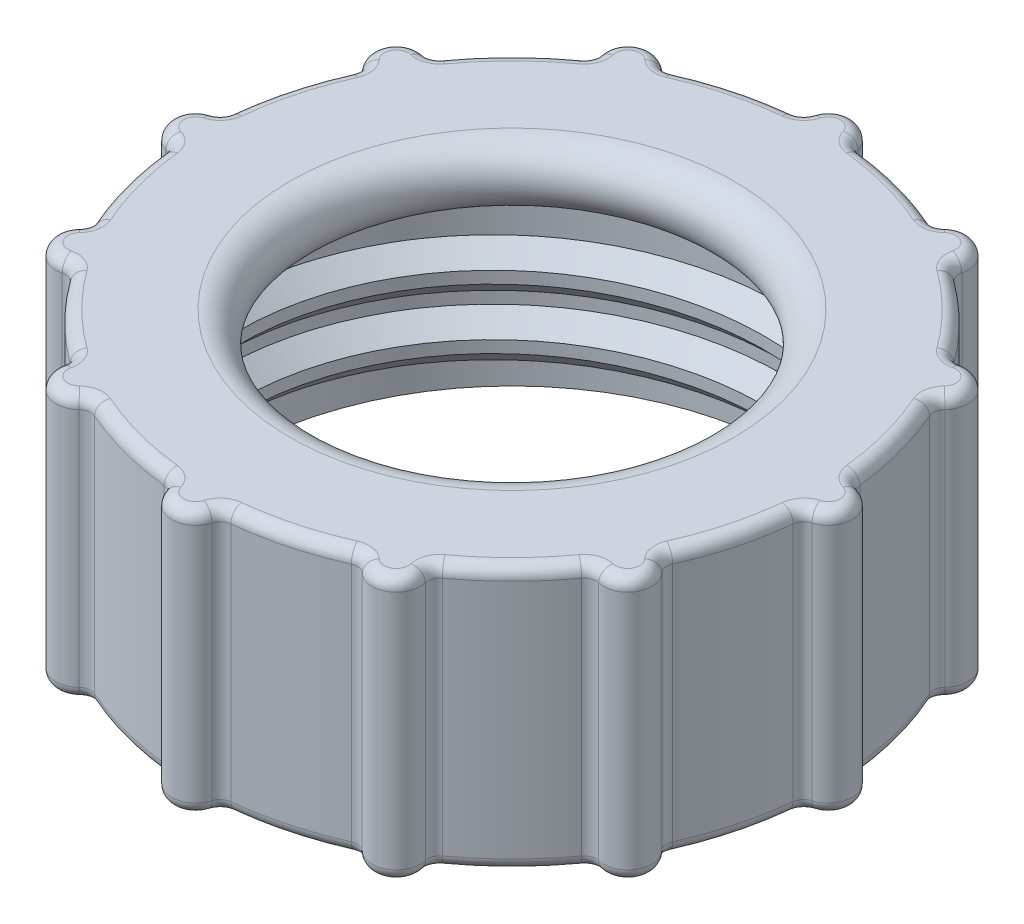
SolidWorks part; units mm, degrees
ref_plane "前视基准面" through (0, 0, 0) normal (0, 0, 1) x (1, 0, 0)
ref_plane "上视基准面" through (0, 0, 0) normal (0, 1, 0) x (1, 0, 0)
ref_plane "右视基准面" through (0, 0, 0) normal (1, 0, 0) x (0, 0, -1)
other "Configuration Table"
sketch "草图1" plane through (0, 0, 0) normal (0, 0, 1) x (1, 0, 0)
  line L0 (0, -5338.8039) -> (0, 261601.3908) construction
  line L1 (0, 32.3027) -> (0, 28.3027)
  line L7 (0, 0) -> (-18.1735, 0) construction
  line L8 (-18.1735, 0) -> (-12.4, 10) construction
  line L9 (-12.4, 10) -> (0, 10) construction
  line L10 (-18.1735, 0) -> (-23.3, 0) construction
  line L11 (-23.3, 0) -> (-23.3, -23.1259) construction
  line L12 (-23.3, 2) -> (0, 2) construction
  line L13 (-18.4622, 7) -> (-23.3, 7)
  line L14 (-23.3, 7) -> (-26.3, 7)
  line L15 (-26.3, 7) -> (-26.3, -15)
  line L16 (-26.3, -15) -> (-23.3, -15)
  line L17 (-23.3, -15) -> (-23.3, 0)
  line L18 (-23.3, 0) -> (-21.3, 2)
  line L19 (-21.3, 2) -> (-18.4622, 2)
  arc A1 (-18.4622, 2) -> (-18.4622, 7) centre (-18.4622, 4.5) ccw
  dimension "D1" = 2
  dimension "D2" = 60
  dimension "D3" = 12.4
  dimension "D4" = 10
  dimension "D5" = 23.3
  dimension "D6" = 45
  dimension "D7" = 3
  dimension "D8" = 3
  dimension "D9" = 15
revolve "旋转1" add sketch "草图1" angle 360 about L0
ref_plane "基准面1" through (0, -13, 0) normal (0, -1, 0) x (-1, 0, 0)
sketch "草图2" plane through (0, -13, 0) normal (0, -1, 0) x (-1, 0, 0)
  circle A0 centre (0, 0) radius 23.3 construction
  circle A1 centre (0, 0) radius 23.3
curve "螺旋线/涡状线1" pitch 5 height 10 turns 2
sketch "草图3" plane through (0, 0, 0) normal (0, 0, 1) x (1, 0, 0)
  line L0 (-23.3, 0) -> (-23.3, -15)
  line L1 (23.3, -15) -> (23.3, 0)
  line L2 (23.3, -15) -> (23.3, -11)
  line L3 (-23.3, 0) -> (-23.3, -15)
  line L4 (23.3, -11) -> (21.8, -12.5)
  line L5 (21.8, -12.5) -> (21.8, -13.5)
  line L6 (21.8, -13.5) -> (23.3, -15)
  point P11 (23.3, -13)
  dimension "D1" = 45
  dimension "D2" = 45
  dimension "D3" = 4
  dimension "D4" = 1.5
sweep "扫描2" add profiles "草图3" path "螺旋线/涡状线1"
sketch "草图7" plane through (0, 7, 0) normal (0, 1, 0) x (1, 0, 0)
  circle A0 centre (0, 0) radius 26.3 construction
  arc A1 (-2.7723, 26.1535) -> (2.7723, 26.1535) centre (0, 0) ccw
  arc A2 (1.9185, 26.8653) -> (-1.9185, 26.8653) centre (0, 26.3) ccw
  arc A3 (-2.7723, 26.1535) -> (-1.9185, 26.8653) centre (-2.8777, 27.1479) ccw
  arc A4 (1.9185, 26.8653) -> (2.7723, 26.1535) centre (2.8777, 27.1479) ccw
  circle A5 centre (0, 0) radius 26.3
  circle M1 centre (0, 0) radius 26.3
  dimension "D1" = 4
  dimension "D2" = 1
  dimension "D3" = 1
extrude "凸台-拉伸1" add sketch "草图7" against normal up to surface (22 mm away) contours A2 M1 up to face at (23.3, -15, 0)
pattern_circular "阵列(圆周)1" count 12 over 360 about axis through (0, 0, 0) along (0, 1, 0) of "凸台-拉伸1"
fillet "圆角1" radius 1 48 edges at (-6.8069, 7, 25.4038) (-2.2373, 7, 26.3798) (2.2373, 7, 26.3798) (0, 7, 28.3) (-18.5969, 7, 18.5969) (-15.1275, 7, 21.7269) (-11.2523, 7, 23.9643) (-14.15, 7, 24.5085) (-25.4038, 7, 6.8069) (-23.9643, 7, 11.2523) (-21.7269, 7, 15.1275) (-24.5085, 7, 14.15) (-25.4038, 7, -6.8069) (-26.3798, 7, -2.2373) (-26.3798, 7, 2.2373) (-28.3, 7, 0) (-18.5969, 7, -18.5969) (-21.7269, 7, -15.1275) (-23.9643, 7, -11.2523) (-24.5085, 7, -14.15) (-6.8069, 7, -25.4038) (-11.2523, 7, -23.9643) (-15.1275, 7, -21.7269) (-14.15, 7, -24.5085) (6.8069, 7, -25.4038) (2.2373, 7, -26.3798) (-2.2373, 7, -26.3798) (0, 7, -28.3) (18.5969, 7, -18.5969) (15.1275, 7, -21.7269) (11.2523, 7, -23.9643) (14.15, 7, -24.5085) (25.4038, 7, -6.8069) (23.9643, 7, -11.2523) (21.7269, 7, -15.1275) (24.5085, 7, -14.15) (25.4038, 7, 6.8069) (26.3798, 7, 2.2373) (26.3798, 7, -2.2373) (28.3, 7, 0) (18.5969, 7, 18.5969) (21.7269, 7, 15.1275) (23.9643, 7, 11.2523) (24.5085, 7, 14.15) (6.8069, 7, 25.4038) (11.2523, 7, 23.9643) (15.1275, 7, 21.7269) (14.15, 7, 24.5085)
fillet "圆角2" radius 1 48 edges at (-6.8069, -15, 25.4038) (-2.2373, -15, 26.3798) (2.2373, -15, 26.3798) (0, -15, 28.3) (-18.5969, -15, 18.5969) (-15.1275, -15, 21.7269) (-11.2523, -15, 23.9643) (-14.15, -15, 24.5085) (-25.4038, -15, 6.8069) (-23.9643, -15, 11.2523) (-21.7269, -15, 15.1275) (-24.5085, -15, 14.15) (-25.4038, -15, -6.8069) (-26.3798, -15, -2.2373) (-26.3798, -15, 2.2373) (-28.3, -15, 0) (-18.5969, -15, -18.5969) (-21.7269, -15, -15.1275) (-23.9643, -15, -11.2523) (-24.5085, -15, -14.15) (-6.8069, -15, -25.4038) (-11.2523, -15, -23.9643) (-15.1275, -15, -21.7269) (-14.15, -15, -24.5085) (6.8069, -15, -25.4038) (2.2373, -15, -26.3798) (-2.2373, -15, -26.3798) (0, -15, -28.3) (18.5969, -15, -18.5969) (15.1275, -15, -21.7269) (11.2523, -15, -23.9643) (14.15, -15, -24.5085) (25.4038, -15, -6.8069) (23.9643, -15, -11.2523) (21.7269, -15, -15.1275) (24.5085, -15, -14.15) (25.4038, -15, 6.8069) (26.3798, -15, 2.2373) (26.3798, -15, -2.2373) (28.3, -15, 0) (18.5969, -15, 18.5969) (21.7269, -15, 15.1275) (23.9643, -15, 11.2523) (24.5085, -15, 14.15) (6.8069, -15, 25.4038) (11.2523, -15, 23.9643) (15.1275, -15, 21.7269) (14.15, -15, 24.5085)
